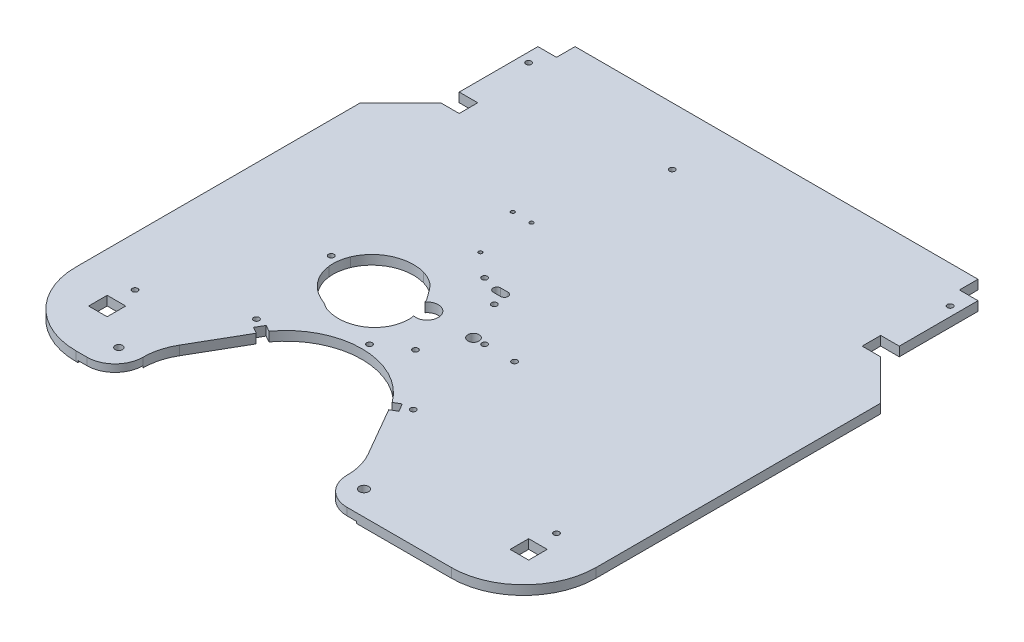
SolidWorks part; units mm, degrees
material "ABS PC"
ref_plane "Plan de face" through (0, 0, 0) normal (0, 0, 1) x (1, 0, 0)
ref_plane "Plan de dessus" through (0, 0, 0) normal (0, 1, 0) x (1, 0, 0)
ref_plane "Plan de droite" through (0, 0, 0) normal (1, 0, 0) x (0, 0, -1)
sketch "Esquisse1" plane through (0, 0, 0) normal (0, 1, 0) x (1, 0, 0)
  line L1 (-140.1, 31.2) -> (140.1, 31.2)
  line L2 (-140.1, 31.2) -> (-140.1, -245.0829)
  line L3 (-140.1, -245.0829) -> (140.1, -245.0829)
  line L4 (140.1, 31.2) -> (140.1, -245.0829)
  line L5 (45, -245.0829) -> (50, -245.0829) construction
  line L6 (-113.5, 31.2) -> (113.5, 31.2) construction
  line L7 (140.1, -4) -> (140.1, 4) construction
  line L8 (-140.1, 4) -> (-140.1, -4) construction
extrude "Boss.-Extru.1" add sketch "Esquisse1" along normal blind 5
sketch "Esquisse2" plane through (0, 0, 0) normal (0, 1, 0) x (1, 0, 0)
  line L3 (-58.1815, -184) -> (-61.6457, -182)
  line L4 (-61.6457, -182) -> (-64.1457, -186.3301)
  line L5 (-64.1457, -186.3301) -> (-60.6815, -188.3301)
  line L7 (-25, -132) -> (-25, -245.0829) construction
  line L8 (-58.1815, -184) -> (-60.6815, -188.3301) construction
  line L9 (-62.6323, -132) -> (62.6323, -132) construction
  line L10 (-25, -62.6323) -> (-25, 62.6323) construction
  line L11 (-60.6815, -188.3301) -> (-75.8539, -214.6094)
  line L13 (-58.1815, -184) -> (-54.7174, -186) construction
  line L14 (-25, -168.5125) -> (-25, -231.5125) construction
  line L16 (140.1, -245.0829) -> (-140.1, -245.0829) construction
  line L17 (-140.1, -245.0829) -> (140.1, -245.0829) construction
  line L18 (8.1815, -184) -> (4.7174, -186) construction
  line L20 (8.1815, -184) -> (10.6815, -188.3301) construction
  line L21 (10.6815, -188.3301) -> (25.8539, -214.6094)
  line L22 (14.1457, -186.3301) -> (10.6815, -188.3301)
  line L23 (11.6457, -182) -> (14.1457, -186.3301)
  line L24 (8.1815, -184) -> (11.6457, -182)
  line L25 (-62.8957, -184.1651) -> (-67.2258, -181.6651) construction
  line L26 (-95, -245.0829) -> (45, -245.0829)
  arc A1 (8.1815, -184) -> (-58.1815, -184) centre (-25, -208.0829) ccw
  arc A2 (-95, -245.0829) -> (-80, -230.0829) centre (-95, -230.0829) ccw
  arc A3 (-95, -245.0829) -> (-86.2863, -217.8734) centre (-95, -230.0829) ccw construction
  arc A4 (-80, -230.0829) -> (-75.8539, -214.6094) centre (-49.0531, -230.0829) cw
  arc A5 (30, -230.0829) -> (25.8539, -214.6094) centre (-0.9469, -230.0829) ccw
  arc A6 (45, -245.0829) -> (30, -230.0829) centre (45, -230.0829) cw
  circle A8 centre (-67.2258, -181.6651) radius 1.5
  circle A10 centre (17.2258, -181.6651) radius 1.5
  dimension "D4" = 41
  dimension "D8" = 5
  dimension "D9" = 3
  dimension "D1" = 4
  dimension "D2" = 52
  dimension "D3" = 37
  dimension "D5" = 90
  dimension "D6" = 5
  dimension "D7" = 30
extrude "Enlèv. mat.-Extru.2" cut sketch "Esquisse2" along normal through all
sketch "Esquisse3" plane through (0, 5, 0) normal (0, 1, 0) x (1, 0, 0)
  line L0 (-30.2198, -127.0596) -> (-26.1089, -139.1328)
  spline S0 degree 3 poles (-37.7914, -122.1402) (-38.0734, -121.8243) (-38.3657, -121.5165) (-38.9965, -120.9381) (-39.3221, -120.6716) (-39.9982, -120.1678) (-40.3476, -119.9323) (-41.0674, -119.4915) (-41.4393, -119.2855) (-41.8168, -119.0963) knots 0 0 0 0 0.25 0.25 0.5 0.5 0.75 0.75 1 1 1 1 construction
  spline S1 degree 3 poles (-32.1541, -129.7487) (-32.3725, -129.4202) (-32.6019, -129.0988) (-33.0628, -128.4574) (-33.2929, -128.1364) (-33.9829, -127.1734) (-34.442, -126.5306) (-35.3645, -125.2486) (-35.8282, -124.6096) (-36.7788, -123.3501) (-37.2654, -122.7294) (-37.7914, -122.1402) knots 0 0 0 0 0.125 0.125 0.25 0.25 0.5 0.5 0.75 0.75 1 1 1 1 construction
  spline S2 degree 3 poles (-35.6619, -154.1946) (-35.0242, -153.7971) (-34.4156, -153.3543) (-33.5487, -152.619) (-33.2665, -152.3609) (-32.7231, -151.8244) (-32.4631, -151.5476) (-31.717, -150.6924) (-31.2669, -150.0877) (-30.6603, -149.1305) (-30.4697, -148.8029) (-30.1129, -148.13) (-29.9465, -147.7839) (-29.4899, -146.7378) (-29.243, -146.0234) (-28.8562, -144.563) (-28.7157, -143.8147) (-28.4532, -141.5381) (-28.491, -140.0256) (-28.7111, -138.5175) knots 0 0 0 0 0.125 0.125 0.1875 0.1875 0.25 0.25 0.375 0.375 0.4375 0.4375 0.5 0.5 0.625 0.625 0.75 0.75 1 1 1 1 construction
  spline S3 degree 3 poles (-35.6619, -154.1946) (-36.3253, -154.608) (-37.0218, -154.968) (-38.4509, -155.5833) (-39.1871, -155.8402) (-40.6929, -156.2533) (-41.4552, -156.4075) (-42.998, -156.615) (-43.7804, -156.6676) (-46.0993, -156.6733) (-47.6259, -156.4799) (-49.5088, -155.9804) (-49.8836, -155.8673) (-50.622, -155.6166) (-50.9867, -155.4786) (-51.7066, -155.1765) (-52.0616, -155.0123) (-52.5826, -154.748) (-52.7564, -154.66) (-53.0886, -154.4564) (-53.2465, -154.3401) (-53.4028, -154.2206) knots 0 0 0 0 0.125 0.125 0.25 0.25 0.375 0.375 0.5 0.5 0.75 0.75 0.8125 0.8125 0.875 0.875 0.9375 0.9375 0.96875 0.96875 1 1 1 1 construction
  spline S4 degree 3 poles (-41.8168, -119.0963) (-42.9717, -118.5173) (-44.1778, -118.0898) (-46.0518, -117.6406) (-46.691, -117.5235) (-47.9689, -117.3572) (-48.6085, -117.3074) (-49.8889, -117.2725) (-50.5296, -117.2869) (-51.8124, -117.3808) (-52.4575, -117.4608) (-54.3583, -117.7944) (-55.5875, -118.1406) (-57.3737, -118.8468) (-57.9613, -119.1147) (-59.1074, -119.714) (-59.6598, -120.0407) (-61.253, -121.1053) (-62.2339, -121.9217) (-63.3433, -123.0959) (-63.5595, -123.3389) (-63.9727, -123.8343) (-64.1705, -124.0875) (-64.7392, -124.8624) (-65.0859, -125.3992) (-65.725, -126.5066) (-66.0166, -127.0778) (-66.4118, -127.9607) (-66.5364, -128.2602) (-66.7677, -128.8619) (-66.8752, -129.1647) (-67.3727, -130.6881) (-67.6417, -131.9376) (-67.7975, -133.5423) (-67.8198, -133.8663) (-67.8456, -134.511) (-67.8492, -134.8322) (-67.832, -135.7928) (-67.7828, -136.429) (-67.6138, -137.6932) (-67.494, -138.3213) (-67.1803, -139.5691) (-66.9857, -140.1898) (-66.3106, -141.9951) (-65.7352, -143.1386) (-64.7029, -144.7728) (-64.3296, -145.3033) (-63.5406, -146.3156) (-63.1238, -146.8009) (-62.2475, -147.7313) (-61.7884, -148.177) (-60.8134, -149.015) (-60.2997, -149.4102) (-59.6532, -149.8941) (-59.524, -149.9912) (-59.2621, -150.18) (-59.1281, -150.2696) (-58.7233, -150.5349) (-58.4482, -150.704) (-57.6091, -151.1904) (-57.0301, -151.4842) (-56.1848, -151.9623) (-55.907, -152.1283) (-55.4954, -152.386) (-55.361, -152.4765) (-55.1045, -152.6783) (-54.9822, -152.7884) (-54.7446, -153.015) (-54.6281, -153.1308) (-54.3929, -153.36) (-54.2744, -153.4736) (-53.9142, -153.8089) (-53.6638, -154.0209) (-53.4028, -154.2206) knots 0 0 0 0 0.0625 0.0625 0.09375 0.09375 0.125 0.125 0.15625 0.15625 0.1875 0.1875 0.25 0.25 0.28125 0.28125 0.3125 0.3125 0.375 0.375 0.390625 0.390625 0.40625 0.40625 0.4375 0.4375 0.46875 0.46875 0.484375 0.484375 0.5 0.5 0.5625 0.5625 0.578125 0.578125 0.59375 0.59375 0.625 0.625 0.65625 0.65625 0.6875 0.6875 0.75 0.75 0.78125 0.78125 0.8125 0.8125 0.84375 0.84375 0.875 0.875 0.882812 0.882812 0.890625 0.890625 0.90625 0.90625 0.9375 0.9375 0.953125 0.953125 0.960937 0.960937 0.96875 0.96875 0.976562 0.976562 0.984375 0.984375 1 1 1 1 construction
  spline S30 degree 3 poles (-26.1089, -139.1328) (-25.957, -141.5638) (-26.2233, -144.068) (-26.9566, -146.3908) knots 0 0 0 0 1 1 1 1
  spline S31 degree 3 poles (-26.9566, -146.3908) (-27.2228, -147.2342) (-27.8831, -148.8893) (-29.2029, -151.171) (-30.8763, -153.2749) (-32.1537, -154.4712) (-32.834, -155.0244) knots 0 0 0 0 0.25 0.5 0.75 1 1 1 1
  spline S32 degree 3 poles (-32.834, -155.0244) (-34.0816, -156.0391) (-36.8741, -157.7375) (-39.9456, -158.6891) (-41.5144, -158.9883) knots 0 0 0 0 0.5 1 1 1 1
  spline S33 degree 3 poles (-41.5144, -158.9883) (-44.1178, -159.4848) (-46.8613, -159.4832) (-49.4654, -158.9908) knots 0 0 0 0 1 1 1 1
  spline S34 degree 3 poles (-49.4654, -158.9908) (-49.952, -158.8988) (-50.9201, -158.6805) (-51.9843, -158.3611) (-52.6895, -158.1153) (-53.0279, -157.9903) (-53.4112, -157.8436) (-53.8185, -157.6386) (-54.1411, -157.4539) (-54.4726, -157.2537) (-54.8017, -157.0368) (-54.9983, -156.9002) (-55.0989, -156.8301) knots 0 0 0 0 0.25 0.5 0.5625 0.625 0.6875 0.75 0.8125 0.875 0.9375 1 1 1 1
  spline S35 degree 3 poles (-55.0989, -156.8301) (-55.3218, -156.6748) (-55.8004, -156.3308) (-56.3372, -156.039) (-57.1153, -155.7047) (-58.1073, -155.2831) (-59.4212, -154.7248) (-60.6952, -154.0815) (-61.7162, -153.4751) (-62.6513, -152.8651) (-64.3061, -151.7169) (-66.4424, -149.811) (-68.6708, -147.1371) (-71.0288, -143.199) (-72.0496, -139.8117) (-72.3207, -137.531) knots 0 0 0 0 0.03125 0.0625 0.09375 0.125 0.1875 0.25 0.28125 0.3125 0.375 0.5 0.625 0.75 1 1 1 1
  spline S36 degree 3 poles (-72.3207, -137.531) (-72.524, -135.8208) (-72.4832, -132.3293) (-71.5647, -128.9796) (-70.9127, -127.3896) knots 0 0 0 0 0.5 1 1 1 1
  spline S37 degree 3 poles (-70.9127, -127.3896) (-70.401, -126.1419) (-69.1411, -123.7476) (-66.5657, -120.5334) (-63.4815, -117.9312) (-59.9208, -115.9009) (-56.1194, -114.5638) (-52.0895, -113.8994) (-48.0382, -113.9466) (-45.3685, -114.4522) (-44.0724, -114.8246) knots 0 0 0 0 0.125 0.25 0.375 0.5 0.625 0.75 0.875 1 1 1 1
  spline S38 degree 3 poles (-44.0724, -114.8246) (-43.1335, -115.0943) (-41.3015, -115.7539) (-39.094, -116.9388) (-37.4723, -118.0859) (-36.3006, -119.1013) (-35.2972, -120.193) (-34.6853, -120.94) (-34.3845, -121.3211) knots 0 0 0 0 0.25 0.5 0.625 0.75 0.875 1 1 1 1
  spline S39 degree 3 poles (-34.3845, -121.3211) (-33.6538, -122.2469) (-32.5988, -123.6857) (-31.2416, -125.568) (-30.5443, -126.5566) (-30.2198, -127.0596) knots 0 0 0 0 0.5 0.75 1 1 1 1
  spline S40 degree 3 poles (-544.0684, -2053.4709) (-13.3203, -329.9447) (2.5957, -129.3013) (-46.0518, -117.6406) (-46.691, -117.5235) (-47.9689, -117.3572) (-48.6085, -117.3074) (-49.8889, -117.2725) (-50.5296, -117.2869) (-51.8124, -117.3808) (-52.4575, -117.4608) (-54.3583, -117.7944) (-55.5875, -118.1406) (-57.3737, -118.8468) (-57.9613, -119.1147) (-59.1074, -119.714) (-59.6598, -120.0407) (-61.253, -121.1053) (-62.2339, -121.9217) (-63.3433, -123.0959) (-63.5595, -123.3389) (-63.9727, -123.8343) (-64.1705, -124.0875) (-64.7392, -124.8624) (-65.0859, -125.3992) (-65.725, -126.5066) (-66.0166, -127.0778) (-66.4118, -127.9607) (-66.5364, -128.2602) (-66.7677, -128.8619) (-66.8752, -129.1647) (-67.3727, -130.6881) (-67.6417, -131.9376) (-67.7975, -133.5423) (-67.8198, -133.8663) (-67.8456, -134.511) (-67.8492, -134.8322) (-67.832, -135.7928) (-67.7828, -136.429) (-67.6138, -137.6932) (-67.494, -138.3213) (-67.1803, -139.5691) (-66.9857, -140.1898) (-66.3106, -141.9951) (-65.7352, -143.1386) (-64.7029, -144.7728) (-64.3296, -145.3033) (-63.5406, -146.3156) (-63.1238, -146.8009) (-62.2475, -147.7313) (-61.7884, -148.177) (-60.8134, -149.015) (-60.2997, -149.4102) (-59.6532, -149.8941) (-59.524, -149.9912) (-59.2621, -150.18) (-59.1281, -150.2696) (-58.7233, -150.5349) (-58.4482, -150.704) (-57.6091, -151.1904) (-57.0301, -151.4842) (-56.1848, -151.9623) (-55.907, -152.1283) (-55.4954, -152.386) (-55.361, -152.4765) (-55.1045, -152.6783) (-54.9822, -152.7884) (-54.7446, -153.015) (-54.6281, -153.1308) (-54.3929, -153.36) (-54.2744, -153.4736) (-26.8241, -179.0197) (131.7308, -54.8381) (1346.14, 1273.1767) knots -2.339844 -2.339844 -2.339844 -2.339844 0.0625 0.0625 0.09375 0.09375 0.125 0.125 0.15625 0.15625 0.1875 0.1875 0.25 0.25 0.28125 0.28125 0.3125 0.3125 0.375 0.375 0.390625 0.390625 0.40625 0.40625 0.4375 0.4375 0.46875 0.46875 0.484375 0.484375 0.5 0.5 0.5625 0.5625 0.578125 0.578125 0.59375 0.59375 0.625 0.625 0.65625 0.65625 0.6875 0.6875 0.75 0.75 0.78125 0.78125 0.8125 0.8125 0.84375 0.84375 0.875 0.875 0.882812 0.882812 0.890625 0.890625 0.90625 0.90625 0.9375 0.9375 0.953125 0.953125 0.960937 0.960937 0.96875 0.96875 0.976562 0.976562 0.984375 0.984375 2.762304 2.762304 2.762304 2.762304 only from (-41.8168, -119.0963) to (-53.4028, -154.2206)
  spline S41 degree 3 poles (-1939.2427, 445.2377) (-11.3915, 5.3531) (-2.0926, -139.9279) (-38.4509, -155.5833) (-39.1871, -155.8402) (-40.6929, -156.2533) (-41.4552, -156.4075) (-42.998, -156.615) (-43.7804, -156.6676) (-46.0993, -156.6733) (-47.6259, -156.4799) (-49.5088, -155.9804) (-49.8836, -155.8673) (-50.622, -155.6166) (-50.9867, -155.4786) (-51.7066, -155.1765) (-52.0616, -155.0123) (-52.5826, -154.748) (-52.7564, -154.66) (-62.008, -148.9921) (-46.7728, -99.7044) (-1052.7685, -1886.2862) knots -6.110057 -6.110057 -6.110057 -6.110057 0.125 0.125 0.25 0.25 0.375 0.375 0.5 0.5 0.75 0.75 0.8125 0.8125 0.875 0.875 0.9375 0.9375 0.96875 0.96875 2.678123 2.678123 2.678123 2.678123 only from (-35.6619, -154.1946) to (-53.4028, -154.2206)
  spline S42 degree 3 poles (805.3246, -1958.3687) (-625.9447, 427.7737) (-104.0787, -212.4384) (-33.5487, -152.619) (-33.2665, -152.3609) (-32.7231, -151.8244) (-32.4631, -151.5476) (-31.717, -150.6924) (-31.2669, -150.0877) (-30.6603, -149.1305) (-30.4697, -148.8029) (-30.1129, -148.13) (-29.9465, -147.7839) (-29.4899, -146.7378) (-29.243, -146.0234) (-28.8562, -144.563) (-28.7157, -143.8147) (-20.1781, -69.7717) (-507.9815, -8.4894) (1948.7508, 124.0064) knots -15.067184 -15.067184 -15.067184 -15.067184 0.125 0.125 0.1875 0.1875 0.25 0.25 0.375 0.375 0.4375 0.4375 0.5 0.5 0.625 0.625 0.75 0.75 12.82174 12.82174 12.82174 12.82174 only from (-35.6619, -154.1946) to (-28.7111, -138.5175)
  spline S43 degree 3 poles (-1678.0425, -1265.3241) (-10.5484, -165.9011) (-20.1896, -146.3733) (-33.0628, -128.4574) (-33.2929, -128.1364) (-33.9829, -127.1734) (-34.442, -126.5306) (-35.3645, -125.2486) (-35.8282, -124.6096) (-54.2717, -100.1715) (-88.436, -89.3419) (-1650.9877, -1303.2795) knots -6.732601 -6.732601 -6.732601 -6.732601 0.125 0.125 0.25 0.25 0.5 0.5 0.75 0.75 10.201277 10.201277 10.201277 10.201277 only from (-32.1541, -129.7487) to (-37.7914, -122.1402)
  spline S44 degree 3 poles (1561.6634, 1077.8271) (-67.121, -199.6011) (-22.5068, -136.058) (-38.9965, -120.9381) (-39.3221, -120.6716) (-39.9982, -120.1678) (-40.3476, -119.9323) (-65.1031, -104.7717) (-144.7605, -156.1255) (1752.928, -999.5442) knots -12.570471 -12.570471 -12.570471 -12.570471 0.25 0.25 0.5 0.5 0.75 0.75 17.69557 17.69557 17.69557 17.69557 only from (-37.7914, -122.1402) to (-41.8168, -119.0963)
extrude "Enlèv. mat.-Extru.3" cut sketch "Esquisse3" against normal through all
sketch "Esquisse4" plane through (0, 5, 0) normal (0, 1, 0) x (1, 0, 0)
  circle A0 centre (-48.2, -62.65) radius 1
  circle A1 centre (-38.1, -62.65) radius 1
  circle A2 centre (-38.1, -90.25) radius 1
  dimension "D1" = 2
extrude "Enlèv. mat.-Extru.4" cut sketch "Esquisse4" against normal through all
sketch "Esquisse5" plane through (0, 5, 0) normal (0, 1, 0) x (1, 0, 0)
  circle A0 centre (22.1224, -132) radius 1.5
  circle A1 centre (-10.0508, -153.25) radius 1.5
  circle A2 centre (-25, -163) radius 1.5
  circle A3 centre (-10.0508, -110.75) radius 1.5
  circle A4 centre (-25, -101) radius 1.5
  circle A5 centre (-76.6, -132) radius 1.5
  circle A6 centre (6, -132) radius 1.5 construction
  circle A7 centre (6, -132) radius 1.5
  circle A8 centre (0, -132) radius 3
  arc A9 (1.5616, -134.5616) -> (1.5616, -129.4384) centre (0, -132) ccw construction
  dimension "D1" = 3
extrude "Enlèv. mat.-Extru.5" cut sketch "Esquisse5" against normal through all
sketch "Esquisse6" plane through (0, 5, 0) normal (0, 1, 0) x (1, 0, 0)
  circle A0 centre (-25, -132) radius 6
  circle A1 centre (-25, -132) radius 5.4 construction
  dimension "D1" = 12
extrude "Enlèv. mat.-Extru.6" cut sketch "Esquisse6" against normal through all
sketch "Esquisse7" plane through (0, 5, 0) normal (0, 1, 0) x (1, 0, 0)
  line L1 (-16, -103.4) -> (-12, -103.4) construction
  line L2 (-16, -101.4) -> (-12, -101.4)
  line L3 (-16, -105.4) -> (-12, -105.4)
  arc A0 (-16, -101.4) -> (-16, -105.4) centre (-16, -103.4) ccw
  arc A6 (-12, -105.4) -> (-12, -101.4) centre (-12, -103.4) ccw
  arc A7 (-11.4091, -103.2958) -> (-12.5909, -103.2958) centre (-12, -103.4) ccw construction
  arc A9 (-15.4091, -103.2958) -> (-16.5909, -103.2958) centre (-16, -103.4) ccw construction
  point P2 (-14, -103.4)
  dimension "D1" = 4
extrude "Enlèv. mat.-Extru.7" cut sketch "Esquisse7" against normal through all
sketch "Esquisse8" plane through (0, 5, 0) normal (0, 1, 0) x (1, 0, 0)
  line L0 (140.1, -245.0829) -> (140.1, 31.2) construction
  line L1 (101.1, -245.0829) -> (140.1, -245.0829)
  line L2 (140.1, -245.0829) -> (140.1, -206.0829)
  line L3 (-140.1, -245.0829) -> (-140.1, -206.0829)
  line L4 (-140.1, 31.2) -> (-140.1, -245.0829) construction
  line L5 (-140.1, -245.0829) -> (-95, -245.0829) construction
  line L6 (-101.1, -245.0829) -> (-140.1, -245.0829)
  arc A0 (140.1, -206.0829) -> (101.1, -245.0829) centre (101.1, -206.0829) cw
  arc A1 (-140.1, -206.0829) -> (-101.1, -245.0829) centre (-101.1, -206.0829) ccw
extrude "Enlèv. mat.-Extru.8" cut sketch "Esquisse8" against normal through all
sketch "Esquisse9" plane through (0, 5, 0) normal (0, 1, 0) x (1, 0, 0)
  line L0 (-108.5, 21.2) -> (-118.5, 21.2) construction
  line L1 (-108.5, 21.2) -> (-108.5, 31.2) construction
  line L2 (-108.5, -31.2) -> (-108.5, -21.2) construction
  line L3 (-108.5, -21.2) -> (-118.5, -21.2) construction
  line L4 (-108.5, -31.2) -> (-118.5, -31.2) construction
  line L5 (-108.5, 21.2) -> (-118.5, 21.2)
  line L6 (-108.5, 21.2) -> (-108.5, 31.2)
  line L7 (-108.5, -31.2) -> (-108.5, -21.2)
  line L8 (-108.5, -21.2) -> (-118.5, -21.2)
  line L9 (-108.5, -31.2) -> (-118.5, -31.2)
  line L10 (-118.5, -21.2) -> (-118.5, 21.2)
  line L11 (-118.5, -31.2) -> (-140.1, -52.8)
  line L12 (-140.1, 31.2) -> (-140.1, -206.0829) construction
  line L13 (-140.1, -52.8) -> (-140.1, 31.2)
  line L14 (-140.1, 31.2) -> (-108.5, 31.2)
  line L15 (0, 0) -> (0, 79.4635) construction
  line L16 (140.1, 31.2) -> (108.5, 31.2)
  line L17 (140.1, -52.8) -> (140.1, 31.2)
  line L18 (118.5, -31.2) -> (140.1, -52.8)
  line L19 (118.5, -21.2) -> (118.5, 21.2)
  line L20 (108.5, -31.2) -> (118.5, -31.2)
  line L21 (108.5, -21.2) -> (118.5, -21.2)
  line L22 (108.5, -31.2) -> (108.5, -21.2)
  line L23 (108.5, 21.2) -> (108.5, 31.2)
  line L24 (108.5, 21.2) -> (118.5, 21.2)
  dimension "D1" = 45
extrude "Enlèv. mat.-Extru.9" cut sketch "Esquisse9" against normal through all
sketch "Esquisse10" plane through (0, 0, 0) normal (0, -1, 0) x (1, 0, 0)
  line L1 (50, 242.0829) -> (50, 245.0829) construction
  line L2 (50, 245.0829) -> (45, 245.0829) construction
  line L3 (45, 242.0829) -> (50, 242.0829) construction
  line L5 (50, 242.0829) -> (50, 245.0829)
  line L6 (50, 245.0829) -> (45, 245.0829)
  line L7 (45, 242.0829) -> (50, 242.0829)
  line L9 (-88.029, 220.3153) -> (-86.2863, 217.8734)
  line L10 (-95, 245.0829) -> (-95, 242.0829)
  line L15 (-95, 242.0829) -> (-95, 245.0829)
  line L16 (-95, 245.0829) -> (-100, 245.0829)
  line L17 (-100, 245.0829) -> (-100, 242.0829)
  line L18 (-100, 242.0829) -> (-95, 242.0829)
  line L20 (-95, 245.0829) -> (-100, 245.0829)
  line L21 (-100, 245.0829) -> (-100, 242.0829)
  line L22 (-100, 242.0829) -> (-95, 242.0829)
  arc A0 (-88.029, 220.3153) -> (-25, 23.5) centre (-25, 132) ccw construction
  arc A1 (-86.2863, 217.8734) -> (-25, 26.5) centre (-25, 132) ccw construction
  arc A2 (-25, 26.5) -> (36.2863, 217.8734) centre (-25, 132) ccw construction
  arc A3 (-25, 23.5) -> (38.029, 220.3153) centre (-25, 132) ccw construction
  arc A4 (-88.029, 220.3153) -> (-25, 23.5) centre (-25, 132) ccw
  arc A5 (-86.2863, 217.8734) -> (-25, 26.5) centre (-25, 132) ccw
  arc A6 (-25, 26.5) -> (36.2863, 217.8734) centre (-25, 132) ccw
  arc A7 (-25, 23.5) -> (38.029, 220.3153) centre (-25, 132) ccw
  arc A8 (45, 245.0829) -> (36.2863, 217.8734) centre (45, 230.0829) ccw construction
  arc A9 (45, 242.0829) -> (38.029, 220.3153) centre (45, 230.0829) ccw construction
  arc A10 (45, 245.0829) -> (36.2863, 217.8734) centre (45, 230.0829) ccw
  arc A11 (45, 242.0829) -> (38.029, 220.3153) centre (45, 230.0829) ccw
  arc A14 (-86.2863, 217.8734) -> (-95, 245.0829) centre (-95, 230.0829) ccw
  arc A15 (-88.029, 220.3153) -> (-95, 242.0829) centre (-95, 230.0829) ccw
  arc A16 (-86.2863, 217.8734) -> (-95, 245.0829) centre (-95, 230.0829) ccw
  arc A17 (-88.029, 220.3153) -> (-95, 242.0829) centre (-95, 230.0829) ccw
  dimension "D1" = 0
  dimension "D2" = 0
extrude "Enlèv. mat.-Extru.10" cut sketch "Esquisse10" against normal blind 1
sketch "Esquisse11" plane through (0, 5, 0) normal (0, 1, 0) x (1, 0, 0)
  line L4 (-118.5, -210.8) -> (-118.5, -220.8)
  line L5 (-108.5, -210.8) -> (-118.5, -210.8)
  line L6 (-108.5, -220.8) -> (-108.5, -210.8)
  line L7 (-118.5, -220.8) -> (-108.5, -220.8)
  line L8 (-118.5, -210.8) -> (-118.5, -220.8)
  line L9 (-108.5, -210.8) -> (-118.5, -210.8)
  line L10 (-108.5, -220.8) -> (-108.5, -210.8)
  line L11 (-118.5, -220.8) -> (-108.5, -220.8)
  line L12 (108.5, -210.8) -> (108.5, -220.8)
  line L13 (118.5, -210.8) -> (108.5, -210.8)
  line L14 (118.5, -220.8) -> (118.5, -210.8)
  line L15 (108.5, -220.8) -> (118.5, -220.8)
  line L16 (108.5, -210.8) -> (108.5, -220.8)
  line L17 (118.5, -210.8) -> (108.5, -210.8)
  line L18 (118.5, -220.8) -> (118.5, -210.8)
  line L19 (108.5, -220.8) -> (118.5, -220.8)
  dimension "D1" = 0
  dimension "D2" = 0
extrude "Enlèv. mat.-Extru.11" cut sketch "Esquisse11" against normal through all
sketch "Esquisse12" plane through (0, 5, 0) normal (0, 1, 0) x (1, 0, 0)
  circle A0 centre (41, -232) radius 2.5 construction
  circle A1 centre (41, -232) radius 2.5
  circle A2 centre (-91, -232) radius 2 construction
  circle A3 centre (-91, -232) radius 2
extrude "Enlèv. mat.-Extru.12" cut sketch "Esquisse12" against normal through all
sketch "Esquisse13" plane through (0, 5, 0) normal (0, 1, 0) x (1, 0, 0)
  circle A0 centre (-113.5, -200.8) radius 1.5
  circle A1 centre (-113.5, 11.2) radius 1.5
  circle A2 centre (-113.5, 11.2) radius 1.525 construction
  circle A3 centre (-113.5, -200.8) radius 1.525 construction
  circle A4 centre (113.5, 11.2) radius 1.5
  circle A5 centre (113.5, -200.8) radius 1.5
  circle A6 centre (113.5, -200.8) radius 1.25 construction
  circle A7 centre (-25, 0) radius 1.5
  circle A9 centre (-25, 0) radius 1.5 construction
  dimension "D1" = 3
extrude "Enlèv. mat.-Extru.15" cut sketch "Esquisse13" against normal through all
